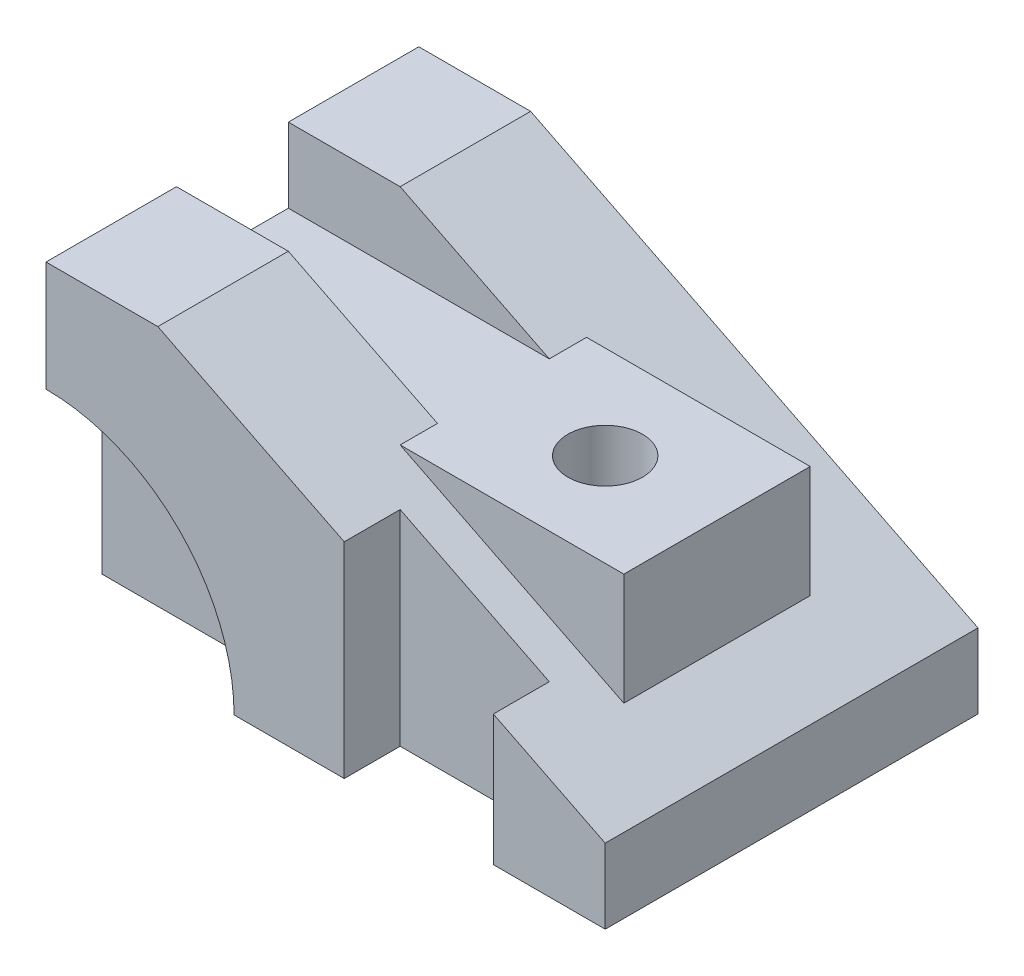
SolidWorks part; units mm, degrees
ref_plane "Front Plane" through (0, 0, 0) normal (0, 0, 1) x (1, 0, 0)
ref_plane "Top Plane" through (0, 0, 0) normal (0, 1, 0) x (1, 0, 0)
ref_plane "Right Plane" through (0, 0, 0) normal (1, 0, 0) x (0, 0, -1)
sketch "Sketch1" plane through (0, 0, 0) normal (0, 0, 1) x (1, 0, 0)
  line L0 (0, 0) -> (0, 80)
  line L1 (0, 80) -> (30, 80)
  line L2 (30, 80) -> (150, 20)
  line L3 (150, 20) -> (150, 0)
  line L4 (150, 0) -> (0, 0)
  dimension "D1" = 80
  dimension "D2" = 30
  dimension "D3" = 20
  dimension "D4" = 150
extrude "Boss-Extrude1" add sketch "Sketch1" against normal blind 50 and the other way blind 50
sketch "Sketch6" plane through (0, 0, 50) normal (0, 0, 1) x (1, 0, 0)
  line L0 (0, 0) -> (150, 0) construction
  line L1 (0, 80) -> (0, 0) construction
  arc A0 (0, 50.4505) -> (50.4505, 0) centre (0, 0) cw
  point P6 (0, 0)
  point P9 (0, 0)
  point P10 (0, 0)
extrude "Cut-Extrude2" cut sketch "Sketch6" against normal blind 15 and the other way through all flip side to cut contours A0
sketch "Sketch7" plane through (0, 0, 0) normal (0, 0, 1) x (1, 0, 0)
  line L0 (70, 60) -> (130, 60)
  line L1 (150, 20) -> (30, 80) construction
  line L2 (130, 60) -> (130, 30)
  line L3 (130, 30) -> (70, 60)
  line L4 (150, 0) -> (150, 20) construction
  dimension "D1" = 20
  dimension "D2" = 30
extrude "Boss-Extrude2" add sketch "Sketch7" along normal blind 25 and the other way blind 25
sketch "Sketch8" plane through (0, 60, 0) normal (0, 1, 0) x (1, 0, 0)
  line L0 (70, -25) -> (130, -25) construction
  line L2 (130, 25) -> (130, -25) construction
  circle A0 centre (100, 0) radius 10
  point P4 (0, 0)
  point P6 (111.0735, 12.4927)
  dimension "D1" = 20
  dimension "D2" = 25
  dimension "D3" = 30
extrude "Cut-Extrude3" cut sketch "Sketch8" against normal through all contours A0
sketch "Sketch11" plane through (0, 0, 0) normal (1, 0, 0) x (0, 0, -1)
  line L0 (25, 60) -> (-25, 60) construction
  line L1 (-15, 80) -> (15, 80)
  line L2 (-15, 80) -> (-15, 60)
  line L3 (-15, 60) -> (15, 60)
  line L4 (15, 80) -> (15, 60)
  line L5 (-50, 20) -> (-50, 80) construction
  line L6 (50, 20) -> (50, 80) construction
  dimension "D1" = 35
  dimension "D2" = 35
  dimension "D3" = 20
extrude "Cut-Extrude5" cut sketch "Sketch11" along normal up to next
sketch "Sketch14" plane through (0, 0, 0) normal (0, -1, 0) x (1, 0, 0)
  line L0 (50.4505, 50) -> (150, 50) construction
  line L1 (80, 50) -> (120, 50)
  line L2 (80, 50) -> (80, 35)
  line L3 (80, 35) -> (120, 35)
  line L4 (120, 50) -> (120, 35)
  line L5 (150, 50) -> (150, -50) construction
  dimension "D1" = 40
  dimension "D2" = 30
  dimension "D3" = 15
extrude "Cut-Extrude8" cut sketch "Sketch14" against normal up to next
